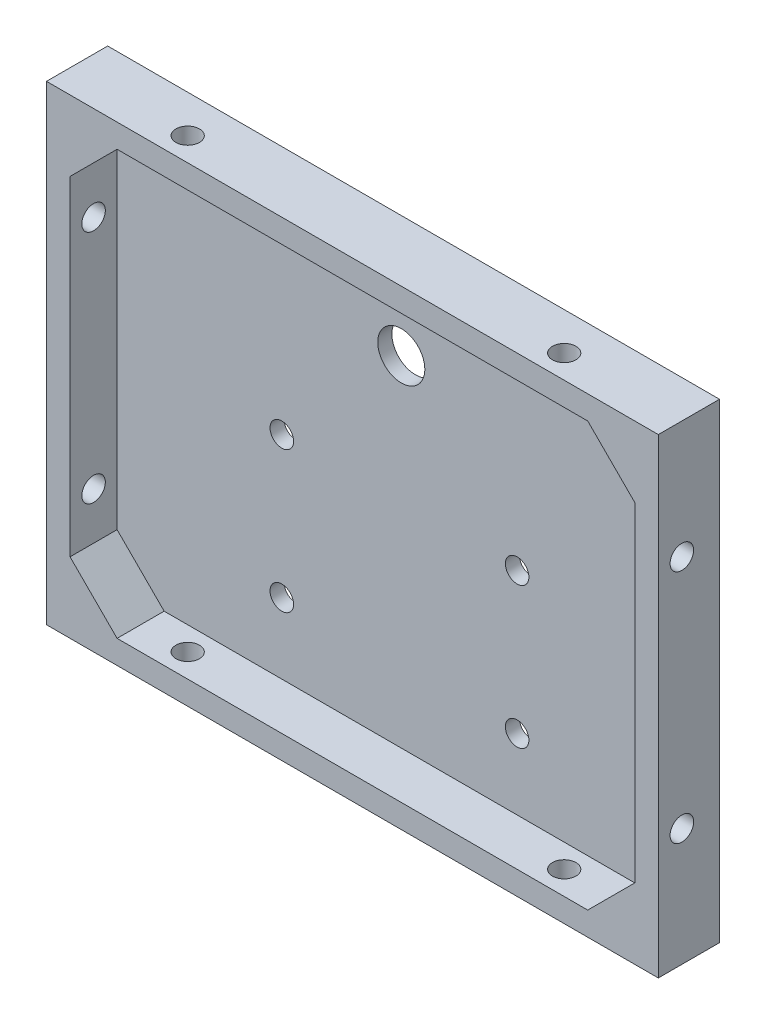
SolidWorks part; units mm, degrees
ref_plane "Plan de face" through (0, 0, 0) normal (0, 0, 1) x (1, 0, 0)
ref_plane "Plan de dessus" through (0, 0, 0) normal (0, 1, 0) x (1, 0, 0)
ref_plane "Plan de droite" through (0, 0, 0) normal (1, 0, 0) x (0, 0, -1)
sketch "Esquisse1" plane through (0, 0, 0) normal (0, 0, 1) x (1, 0, 0)
  line L0 (44.1184, 33.7284) -> (54.1184, 33.7284)
  line L1 (-75.8816, 33.7284) -> (44.1184, 33.7284)
  line L2 (-75.8816, 33.7284) -> (-75.8816, -66.2716)
  line L3 (-75.8816, -66.2716) -> (54.1184, -66.2716)
  line L4 (54.1184, 23.7284) -> (54.1184, -66.2716)
  line L5 (54.1184, 33.7284) -> (54.1184, 23.7284)
  point P6 (54.1184, 33.7284)
  dimension "D1" = 130
  dimension "D2" = 100
extrude "Boss.-Extru.1" add sketch "Esquisse1" along normal blind 13
shell "Coque1" thickness 5 removed face at (-10.8816, -16.2716, 13)
sketch "Esquisse2" plane through (-75.8816, 0, 0) normal (-1, 0, 0) x (0, 0, 1)
  line L0 (13, 33.7284) -> (13, -66.2716) construction
  line L1 (13, 33.7284) -> (0, 33.7284) construction
  line L2 (13, -66.2716) -> (0, -66.2716) construction
  circle A0 centre (8, 8.7284) radius 2.5
  circle A1 centre (8, -41.2716) radius 2.5
  dimension "D1" = 5
  dimension "D2" = 5
  dimension "D3" = 5
  dimension "D4" = 5
  dimension "D5" = 25
  dimension "D6" = 25
extrude "Enlèv. mat.-Extru.1" cut sketch "Esquisse2" against normal up to surface (130 mm away) contours A1 | A0 region at (-75.8816, -41.2716, 8) up to face at (54.1184, -16.2716, 6.5)
sketch "Esquisse3" plane through (0, -66.2716, 0) normal (0, -1, 0) x (1, 0, 0)
  line L0 (-75.8816, 13) -> (54.1184, 13) construction
  line L2 (54.1184, 13) -> (54.1184, 0) construction
  line L3 (-75.8816, 13) -> (-75.8816, 0) construction
  circle A0 centre (-50.8816, 8) radius 2.5
  circle A1 centre (29.1184, 8) radius 2.5
  dimension "D1" = 5
  dimension "D2" = 5
  dimension "D3" = 5
  dimension "D4" = 5
  dimension "D5" = 25
  dimension "D6" = 25
extrude "Enlèv. mat.-Extru.2" cut sketch "Esquisse3" against normal up to surface (100 mm away) up to face at (-10.8816, 33.7284, 6.5)
sketch "Esquisse4" plane through (0, 0, 3) normal (0, 0, 1) x (1, 0, 0)
  line L0 (-60.8816, 28.7284) -> (-70.8816, 18.7284)
  line L1 (49.1184, 28.7284) -> (-70.8816, 28.7284) construction
  line L2 (-70.8816, 28.7284) -> (-70.8816, -61.2716) construction
  line L3 (-70.8816, 18.7284) -> (-70.8816, 28.7284)
  line L4 (-70.8816, 28.7284) -> (-60.8816, 28.7284)
  line L5 (49.1184, 28.7284) -> (49.1184, 18.7284)
  line L6 (49.1184, -61.2716) -> (49.1184, 28.7284) construction
  line L7 (49.1184, 18.7284) -> (39.1184, 28.7284)
  line L8 (39.1184, 28.7284) -> (49.1184, 28.7284)
  line L9 (49.1184, 28.7284) -> (-70.8816, 28.7284) construction
  line L10 (49.1184, -61.2716) -> (49.1184, -51.2716)
  line L11 (49.1184, -51.2716) -> (39.1184, -61.2716)
  line L12 (-70.8816, -61.2716) -> (49.1184, -61.2716) construction
  line L13 (39.1184, -61.2716) -> (49.1184, -61.2716)
  line L14 (-60.8816, -61.2716) -> (-70.8816, -51.2716)
  line L15 (-70.8816, 28.7284) -> (-70.8816, -61.2716) construction
  line L16 (-70.8816, -51.2716) -> (-70.8816, -61.2716)
  line L17 (-70.8816, -61.2716) -> (-60.8816, -61.2716)
  dimension "D1" = 10
  dimension "D2" = 10
  dimension "D3" = 10
  dimension "D4" = 10
  dimension "D5" = 10
  dimension "D6" = 10
  dimension "D7" = 10
  dimension "D8" = 10
extrude "Boss.-Extru.2" add sketch "Esquisse4" along normal up to surface (10 mm away) up to face at (-10.8816, -16.2716, 13)
sketch "Esquisse6" plane through (0, 0, 3) normal (0, 0, 1) x (1, 0, 0)
  line L0 (-75.8816, -66.2716) -> (54.1184, -66.2716) construction
  line L1 (54.1184, -66.2716) -> (54.1184, 33.7284) construction
  line L2 (-75.8816, 33.7284) -> (-75.8816, -66.2716) construction
  circle A0 centre (-35.8816, -46.2716) radius 2.5
  circle A1 centre (14.1184, -46.2716) radius 2.5
  circle A2 centre (14.1184, -16.2716) radius 2.5
  circle A3 centre (-35.8816, -16.2716) radius 2.5
  dimension "D1" = 5
  dimension "D2" = 5
  dimension "D3" = 5
  dimension "D4" = 5
  dimension "D5" = 20
  dimension "D6" = 20
  dimension "D7" = 50
  dimension "D8" = 50
  dimension "D9" = 30
  dimension "D10" = 40
  dimension "D11" = 40
  dimension "D12" = 40
extrude "Enlèv. mat.-Extru.3" cut sketch "Esquisse6" against normal up to surface (3 mm away) up to face at (-10.8816, -16.2716, 0)
sketch "Esquisse7" plane through (0, 0, 3) normal (0, 0, 1) x (1, 0, 0)
  circle A0 centre (-10.494, 10.9211) radius 5
  dimension "D1" = 10
extrude "Enlèv. mat.-Extru.4" cut sketch "Esquisse7" against normal up to surface (3 mm away) up to face at (-33.3816, -16.2716, 0)
